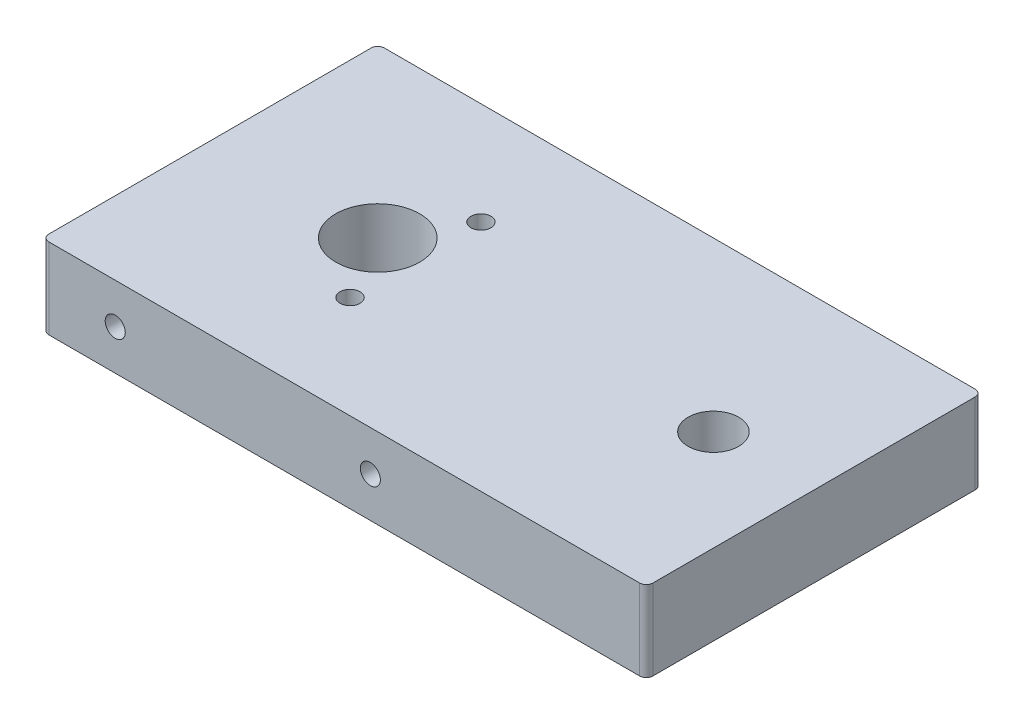
SolidWorks part; units mm, degrees
material "6061-T6 (SS)"
ref_plane "Front Plane" through (0, 0, 0) normal (0, 0, 1) x (1, 0, 0)
ref_plane "Top Plane" through (0, 0, 0) normal (0, 1, 0) x (1, 0, 0)
ref_plane "Right Plane" through (0, 0, 0) normal (1, 0, 0) x (0, 0, -1)
sketch "Sketch1" plane through (0, 0, 0) normal (0, 1, 0) x (1, 0, 0)
  line L0 (-31.75, 0) -> (31.75, 0) construction
  line L2 (50.8, 31.75) -> (-63.5, 31.75)
  line L3 (50.8, 31.75) -> (50.8, -31.75)
  line L4 (50.8, -31.75) -> (-63.5, -31.75)
  line L5 (-63.5, 31.75) -> (-63.5, -31.75)
  line L6 (50.8, 31.75) -> (-63.5, -31.75) construction
  line L7 (50.8, -31.75) -> (-63.5, 31.75) construction
  circle A0 centre (-31.75, 0) radius 19.05 construction
  circle A1 centre (31.75, 0) radius 19.05 construction
  point P3 (-6.35, 0)
  point P4 (31.75, 0)
  dimension "D1" = 19.05
  dimension "D2" = 63.5
  dimension "D3" = 63.5
  dimension "D4" = 114.3
extrude "Boss-Extrude1" add sketch "Sketch1" along normal blind 15.24 contours L4 L5 L2 L3
hole_wizard "5/8 (0.625) Diameter Hole1" positions "Sketch5" profile "Sketch6" hole size "5/8" standard "ANSI Inch" end condition through all
sketch "Sketch5" plane through (0, 15.24, 0) normal (0, 1, 0) x (1, 0, 0)
  point P0 (-31.75, 0)
sketch "Sketch6" plane through (-31.75, 15.24, 0) normal (1, 0, 0) x (0, 0, 1)
  line L0 (0, 0) -> (0, 15.24)
  line L1 (0, 15.24) -> (7.9375, 15.24)
  line L2 (7.9375, 15.24) -> (7.9375, 0)
  line L5 (7.9375, 0) -> (0, 0)
  line L11 (0, -6.35) -> (0, 107.95) construction
  dimension "Thru Hole Dia." = 15.875
  dimension "Thru Hole Depth" = 15.24
hole_wizard "#10-24 Tapped Hole3" positions "Sketch7" profile "Sketch8" tap size "#10-24" standard "ANSI Inch" end condition through all
sketch "Sketch7" plane through (0, 15.24, 0) normal (0, 1, 0) x (1, 0, 0)
  line L1 (-46.0375, 0) -> (-17.4625, 0) construction
  line L3 (-24.6062, -12.3733) -> (-31.75, 0) construction
  circle A0 centre (-31.75, 0) radius 14.2875
  point P16 (-24.6062, 12.3733)
  point P17 (-24.6062, -12.3733)
  dimension "D2" = 28.575
  dimension "D1" = 60
sketch "Sketch8" plane through (-24.6062, 15.24, 12.3733) normal (1, 0, 0) x (0, 0, 1)
  line L0 (0, 0) -> (0, 15.24)
  line L1 (0, 15.24) -> (1.8986, 15.24)
  line L2 (1.8986, 15.24) -> (1.8986, 0)
  line L5 (1.8986, 0) -> (0, 0)
  line L11 (0, -6.35) -> (0, 107.95) construction
  dimension "Thru Tap Drill Dia." = 3.7973
  dimension "Thru Tap Drill Depth" = 15.24
cosmetic thread "Hole Thread1" parameters "D2"=4.826
cosmetic thread "Hole Thread2" parameters "D2"=4.826
sketch "Sketch10" plane through (0, 0, 0) normal (0, -1, 0) x (1, 0, 0)
  point P0 (31.75, 0)
hole_wizard "CBORE for 3/8 Binding Head Machine Screw1" positions "Sketch11" profile "Sketch12" counterbore size "3/8" standard "ANSI Inch" end condition through all
sketch "Sketch11" plane through (0, 0, 0) normal (0, -1, 0) x (-1, 0, 0)
  point P0 (-31.75, 0)
sketch "Sketch12" plane through (31.75, 0, 0) normal (1, 0, 0) x (0, 0, -1)
  line L0 (0, 0) -> (0, 15.24)
  line L1 (0, 15.24) -> (4.7879, 15.24)
  line L3 (4.7879, 15.24) -> (4.7879, 7.62)
  line L4 (4.7879, 7.62) -> (9.525, 7.62)
  line L5 (9.525, 7.62) -> (9.525, 0)
  line L7 (9.525, 0) -> (0, 0)
  line L11 (0, -6.35) -> (0, 107.95) construction
  dimension "Thru Hole Dia." = 9.5758
  dimension "Thru Hole Depth" = 15.24
  dimension "C'Bore Dia." = 19.05
  dimension "C'Bore Depth" = 7.62
sketch "Sketch14" plane through (0, 0, 31.75) normal (0, 0, 1) x (1, 0, 0)
  line L0 (-63.5, 7.62) -> (50.8, 7.62) construction
  line L1 (-63.5, 15.24) -> (-63.5, 0) construction
  line L2 (50.8, 15.24) -> (50.8, 0) construction
  line L3 (-49.657, 15.24) -> (-49.657, 0) construction
  line L4 (50.8, 15.24) -> (-63.5, 15.24) construction
  line L5 (50.8, 0) -> (-63.5, 0) construction
  line L6 (-1.397, 15.24) -> (-1.397, 0) construction
  line L7 (5.0399, 0) -> (-58.4601, 0) construction
  point P14 (-49.657, 7.62)
  point P17 (-1.397, 7.62)
  dimension "D1" = 13.843
  dimension "D2" = 48.26
sketch "Sketch16" plane through (0, 0, -31.75) normal (0, 0, -1) x (-1, 0, 0)
  line L0 (-50.8, 7.62) -> (63.5, 7.62) construction
  line L1 (-50.8, 15.24) -> (-50.8, 0) construction
  line L3 (49.657, 15.24) -> (49.657, 0) construction
  line L5 (1.397, 15.24) -> (1.397, 0) construction
hole_wizard "#10-24 Tapped Hole1" positions "Sketch18" profile "Sketch19" tap size "#10-24" standard "ANSI Inch"
sketch "Sketch18" plane through (0, 0, -31.75) normal (0, 0, -1) x (-1, 0, 0)
  line L1 (49.657, 15.24) -> (49.657, 0) construction
  point P4 (49.657, 7.62)
  point P10 (1.397, 7.62)
sketch "Sketch19" plane through (-49.657, 7.62, -31.75) normal (1, 0, 0) x (0, 1, 0)
  line L0 (0, 0) -> (0, 11.176)
  line L1 (0, 11.176) -> (1.8986, 10.0352)
  line L2 (1.8986, 10.0352) -> (1.8986, 0)
  line L5 (1.8986, 0) -> (0, 0)
  line L10 (0, 11.176) -> (-1.8987, 10.0352) construction
  line L11 (0, -6.35) -> (0, 107.95) construction
  dimension "Tap Drill Dia." = 3.7973
  dimension "Tap Drill Depth" = 11.176
  dimension "Drill Angle" = 118
cosmetic thread "Hole Thread3" parameters "D1"=6.35, "D2"=4.826
cosmetic thread "Hole Thread4" parameters "D1"=6.35, "D2"=4.826
hole_wizard "#10-24 Tapped Hole2" positions "Sketch20" profile "Sketch21" tap size "#10-24" standard "ANSI Inch"
sketch "Sketch20" plane through (0, 0, 31.75) normal (0, 0, 1) x (1, 0, 0)
  line L1 (-49.657, 15.24) -> (-49.657, 0) construction
  point P6 (-49.657, 7.62)
  point P12 (-1.397, 7.62)
sketch "Sketch21" plane through (-49.657, 7.62, 31.75) normal (1, 0, 0) x (0, -1, 0)
  line L0 (0, 0) -> (0, 11.176)
  line L1 (0, 11.176) -> (1.8986, 10.0352)
  line L2 (1.8986, 10.0352) -> (1.8986, 0)
  line L5 (1.8986, 0) -> (0, 0)
  line L10 (0, 11.176) -> (-1.8987, 10.0352) construction
  line L11 (0, -6.35) -> (0, 107.95) construction
  dimension "Tap Drill Dia." = 3.7973
  dimension "Tap Drill Depth" = 11.176
  dimension "Drill Angle" = 118
cosmetic thread "Hole Thread5" parameters "D1"=6.35, "D2"=4.826
cosmetic thread "Hole Thread6" parameters "D1"=6.35, "D2"=4.826
fillet "Fillet1" radius 1.27 4 edges at (50.8, 7.62, 31.75) (50.8, 7.62, -31.75) (-63.5, 7.62, -31.75) (-63.5, 7.62, 31.75)
equation "\"D2@Sketch14\"=1.9in"
